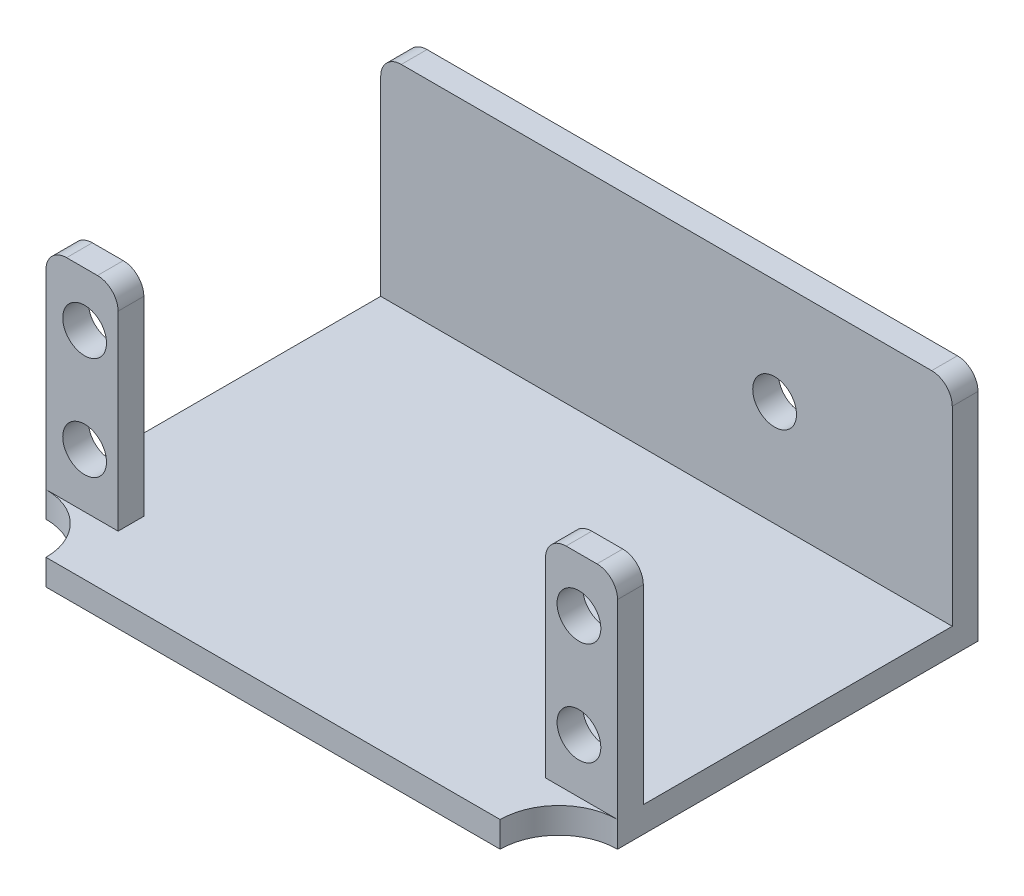
SolidWorks part; units mm, degrees
ref_plane "Front" through (0, 0, 0) normal (0, 0, 1) x (1, 0, 0)
ref_plane "Top" through (0, 0, 0) normal (0, 1, 0) x (1, 0, 0)
ref_plane "Right" through (0, 0, 0) normal (1, 0, 0) x (0, 0, -1)
sketch "Sketch1" plane through (0, 0, 0) normal (0, 1, 0) x (1, 0, 0)
  line L1 (0, 0) -> (55.5, 0)
  line L2 (0, 0) -> (0, 38.2)
  line L3 (0, 38.2) -> (55.5, 38.2)
  line L4 (55.5, 0) -> (55.5, 38.2)
  dimension "D1" = 38.2
  dimension "D2" = 55.5
extrude "bracketBase" add sketch "Sketch1" along normal blind 2.5
ref_plane "referencePlane1" through (0, 0, -8.2) normal (0, 0, 1) x (1, 0, 0)
sketch "Sketch2" plane through (0, 0, -8.2) normal (0, 0, 1) x (1, 0, 0)
  line L0 (27.75, 2.5) -> (27.75, 23) construction
  line L1 (0, 2.5) -> (7, 2.5)
  line L2 (0, 2.5) -> (0, 23)
  line L3 (0, 23) -> (7, 23)
  line L4 (7, 2.5) -> (7, 23)
  line L5 (0, 2.5) -> (55.5, 2.5) construction
  line L6 (55.5, 23) -> (48.5, 23)
  line L7 (48.5, 2.5) -> (48.5, 23)
  line L8 (55.5, 2.5) -> (48.5, 2.5)
  line L9 (55.5, 2.5) -> (55.5, 23)
  dimension "D1" = 20.5
  dimension "D2" = 7
extrude "servoMountingHoleTabs" add sketch "Sketch2" along normal blind 2.5
sketch "Sketch3" plane through (0, 0, -5.7) normal (0, 0, 1) x (1, 0, 0)
  line L0 (0, 12.75) -> (7, 12.75) construction
  line L3 (0, 23) -> (0, 2.5) construction
  line L4 (7, 2.5) -> (7, 23) construction
  line L5 (7, 23) -> (0, 23) construction
  line L6 (27.75, 2.5) -> (27.75, 23) construction
  line L7 (0, 2.5) -> (55.5, 2.5) construction
  circle A0 centre (3.75, 17.75) radius 2.125
  circle A1 centre (3.75, 7.75) radius 2.125
  circle A2 centre (51.75, 7.75) radius 2.125
  circle A3 centre (51.75, 17.75) radius 2.125
  dimension "D1" = 4.25
  dimension "D2" = 3.75
  dimension "D3" = 5.25
extrude "servoMountingHoles" cut sketch "Sketch3" against normal blind 2.5
sketch "Sketch4" plane through (0, 0, 0) normal (0, 1, 0) x (1, 0, 0)
  line L0 (55.5, 8.2) -> (55.5, 38.2) construction
  line L1 (0, 38.2) -> (55.5, 38.2)
  line L2 (0, 38.2) -> (0, 40.7)
  line L3 (0, 40.7) -> (55.5, 40.7)
  line L4 (55.5, 38.2) -> (55.5, 40.7)
  dimension "D1" = 2.5
extrude "baseWall" add sketch "Sketch4" along normal up to surface (23 mm away) up to face at (3.5, 23, -6.95)
sketch "Sketch6" plane through (0, 2.5, 0) normal (0, 1, 0) x (1, 0, 0)
  circle A0 centre (0, 0) radius 5.7
  circle A1 centre (55.5, 0) radius 5.7
extrude "baseTrim" cut sketch "Sketch6" against normal blind 2.5
fillet "Fillet1" radius 2 6 edges at (7, 23, -6.95) (48.5, 23, -6.95) (0, 23, -6.95) (55.5, 23, -6.95) (55.5, 23, -39.45) (0, 23, -39.45)
sketch "Sketch7" plane through (0, 0, -40.7) normal (0, 0, -1) x (-1, 0, 0)
  line L0 (0, 21) -> (0, 0) construction
  line L1 (-55.5, 0) -> (0, 0) construction
  circle A0 centre (-17.25, 12.75) radius 2.125
  dimension "D1" = 4.25
  dimension "D2" = 17.25
  dimension "D3" = 12.75
extrude "M4mountingHole" cut sketch "Sketch7" against normal blind 10
sketch "Sketch8" plane through (0, 0, -40.7) normal (0, 0, -1) x (-1, 0, 0)
  line L0 (-27.75, 23) -> (-27.75, 0) construction
  line L1 (-2, 23) -> (-53.5, 23) construction
  line L2 (-55.5, 0) -> (0, 0) construction
  circle A0 centre (-17.25, 12.75) radius 2.125 construction
  circle A1 centre (-17.25, 12.75) radius 2.125 construction
  circle A2 centre (-38.25, 12.75) radius 2.125
extrude "Cut-Extrude1" cut sketch "Sketch8" against normal blind 10
sketch "Sketch9" plane through (0, 0, -40.7) normal (0, 0, -1) x (-1, 0, 0)
  circle A0 centre (-17.25, 12.75) radius 2.125 construction
  circle A1 centre (-17.25, 12.75) radius 2.125
extrude "Boss-Extrude1" add sketch "Sketch9" against normal up to surface (2.5 mm away) up to face at (36.125, 12.75, -38.2)
